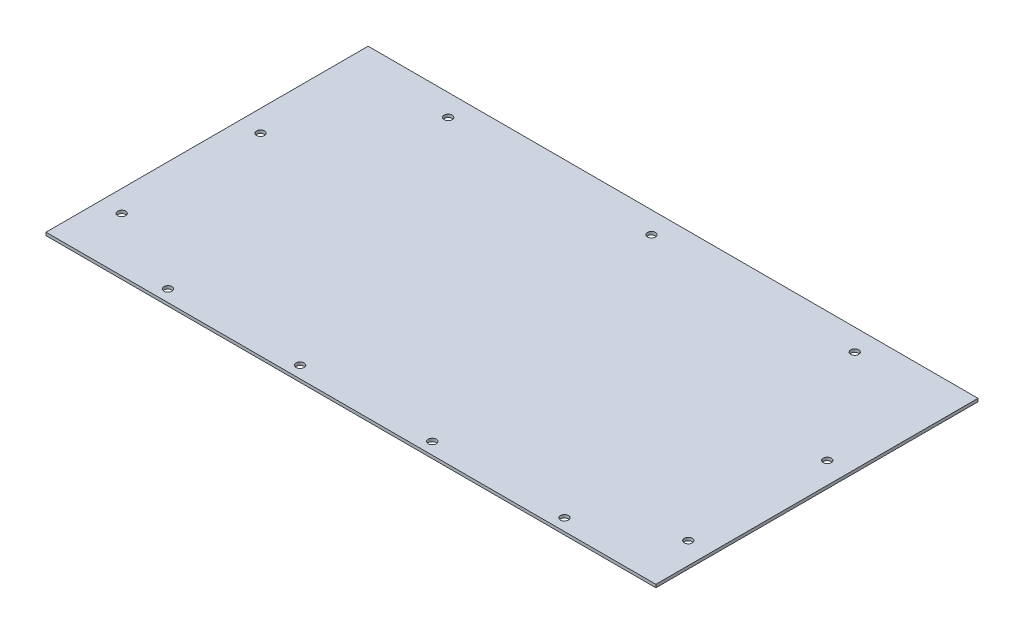
SolidWorks part; units mm, degrees
material "6061-T6 (SS)"
ref_plane "X-Y Datum" through (0, 0, 0) normal (0, 0, 1) x (1, 0, 0)
ref_plane "X-Z Datum" through (0, 0, 0) normal (0, 1, 0) x (1, 0, 0)
ref_plane "Y-Z Datum" through (0, 0, 0) normal (1, 0, 0) x (0, 0, -1)
sketch "Sketch1" plane through (0, 0, 0) normal (0, 0, 1) x (1, 0, 0)
  line L1 (-228.6, -1.143) -> (228.6, -1.143)
  line L2 (-228.6, -1.143) -> (-228.6, 1.143)
  line L3 (-228.6, 1.143) -> (228.6, 1.143)
  line L4 (228.6, -1.143) -> (228.6, 1.143)
  line L5 (-228.6, -1.143) -> (228.6, 1.143) construction
  line L6 (-228.6, 1.143) -> (228.6, -1.143) construction
  point P0 (0, 0)
  dimension "D1" = 2.286
  dimension "D2" = 457.2
extrude "Boss-Extrude1" add sketch "Sketch1" along normal blind 238.3152
sketch "Sketch2" plane through (0, 0, 0) normal (0, 0, -1) x (-1, 0, 0)
  line L22 (-228.6, 1.143) -> (-228.6, -1.143)
  line L23 (-228.6, -1.143) -> (228.6, -1.143)
  line L24 (228.6, -1.143) -> (228.6, 1.143)
  line L25 (228.6, 1.143) -> (-228.6, 1.143)
  line L26 (-228.6, 1.143) -> (-228.6, -1.143)
  line L27 (-228.6, -1.143) -> (228.6, -1.143)
  line L28 (228.6, -1.143) -> (228.6, 1.143)
  line L29 (228.6, 1.143) -> (-228.6, 1.143)
  line M6 (-228.6, -1.143) -> (228.6, -1.143)
  line M8 (228.6, 1.143) -> (-228.6, 1.143)
  dimension "D1" = 0
extrude "Boss-Extrude2" add sketch "Sketch2" along normal blind 3.175 contours M8 M6 | M8 M6 region at (0, 0, 0)
sketch "Sketch8" plane through (0, -1.143, 0) normal (0, -1, 0) x (1, 0, 0)
  circle A0 centre (-212.419, 197.7848) radius 3 construction
  circle A1 centre (-212.419, 93.6448) radius 3 construction
  circle A2 centre (-152.4, 13.0175) radius 3 construction
  circle A3 centre (0, 13.0175) radius 3 construction
  circle A4 centre (152.4, 13.0175) radius 3 construction
  circle A5 centre (212.419, 197.7848) radius 3 construction
  circle A6 centre (212.419, 93.6448) radius 3 construction
  circle A7 centre (-212.419, 197.7848) radius 3
  circle A8 centre (-212.419, 93.6448) radius 3
  circle A9 centre (-152.4, 13.0175) radius 3
  circle A10 centre (0, 13.0175) radius 3
  circle A11 centre (152.4, 13.0175) radius 3
  circle A12 centre (212.419, 197.7848) radius 3
  circle A13 centre (212.419, 93.6448) radius 3
extrude "Cut-Extrude9" cut sketch "Sketch8" against normal blind 3.175
sketch "Sketch9" plane through (0, 1.143, 0) normal (0, 1, 0) x (1, 0, 0)
  line L0 (-146.05, -238.3152) -> (-146.05, -229.4252) construction
  line L1 (228.6, -238.3152) -> (-228.6, -238.3152) construction
  line L2 (-228.6, -238.3152) -> (-228.6, 3.175) construction
  circle A0 centre (-146.05, -229.4252) radius 3
  dimension "D2" = 82.55
  dimension "D3" = 6
  dimension "D1" = 8.89
extrude "Cut-Extrude10" cut sketch "Sketch9" against normal blind 2.54
pattern_linear "LPattern1" count 4 spacing 99.06 along (1, 0, 0) of "Cut-Extrude10"
sketch "Sketch10" plane through (0, -1.143, 0) normal (0, -1, 0) x (1, 0, 0)
  circle A0 centre (151.13, 229.4252) radius 3 construction
  circle A1 centre (52.07, 229.4252) radius 3 construction
  circle A2 centre (-46.99, 229.4252) radius 3 construction
  circle A3 centre (-146.05, 229.4252) radius 3 construction
  circle A4 centre (151.13, 229.4252) radius 3
  circle A5 centre (52.07, 229.4252) radius 3
  circle A6 centre (-46.99, 229.4252) radius 3
  circle A7 centre (-146.05, 229.4252) radius 3
